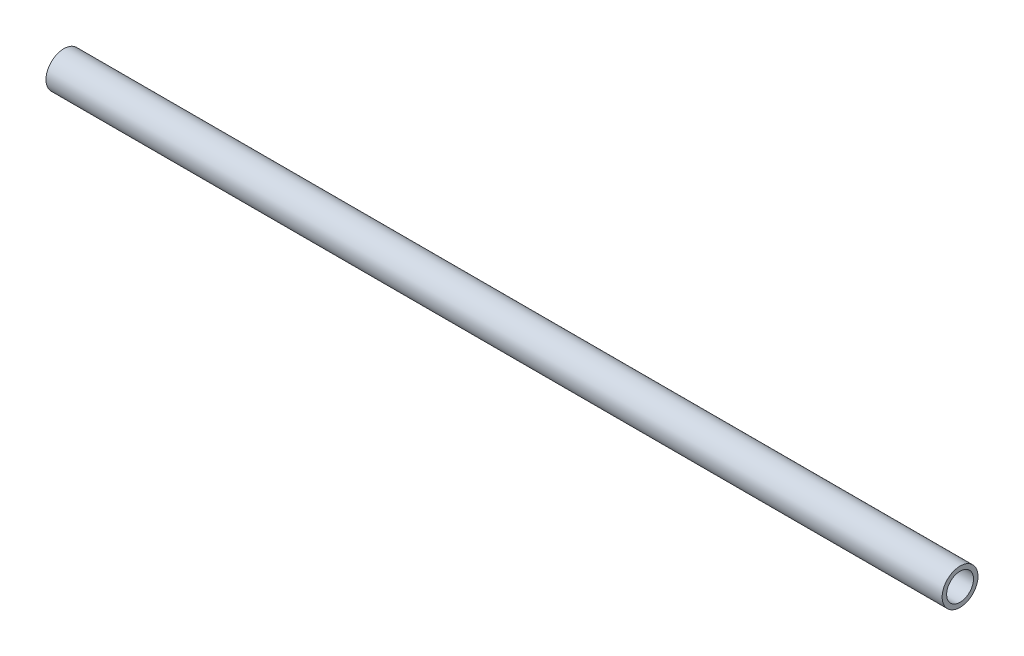
SolidWorks part; units mm, degrees
material "Thornel Mat VMA"
ref_plane "Front" through (0, 0, 0) normal (0, 0, 1) x (1, 0, 0)
ref_plane "Top" through (0, 0, 0) normal (0, 1, 0) x (1, 0, 0)
ref_plane "Right" through (0, 0, 0) normal (1, 0, 0) x (0, 0, -1)
sketch "Sketch1" plane through (0, 0, 0) normal (1, 0, 0) x (0, 0, -1)
  circle A0 centre (0, 0) radius 4
  circle A1 centre (0, 0) radius 3
  dimension "D1" = 8
  dimension "D2" = 6
extrude "Boss-Extrude1" add sketch "Sketch1" along normal mid plane 200
